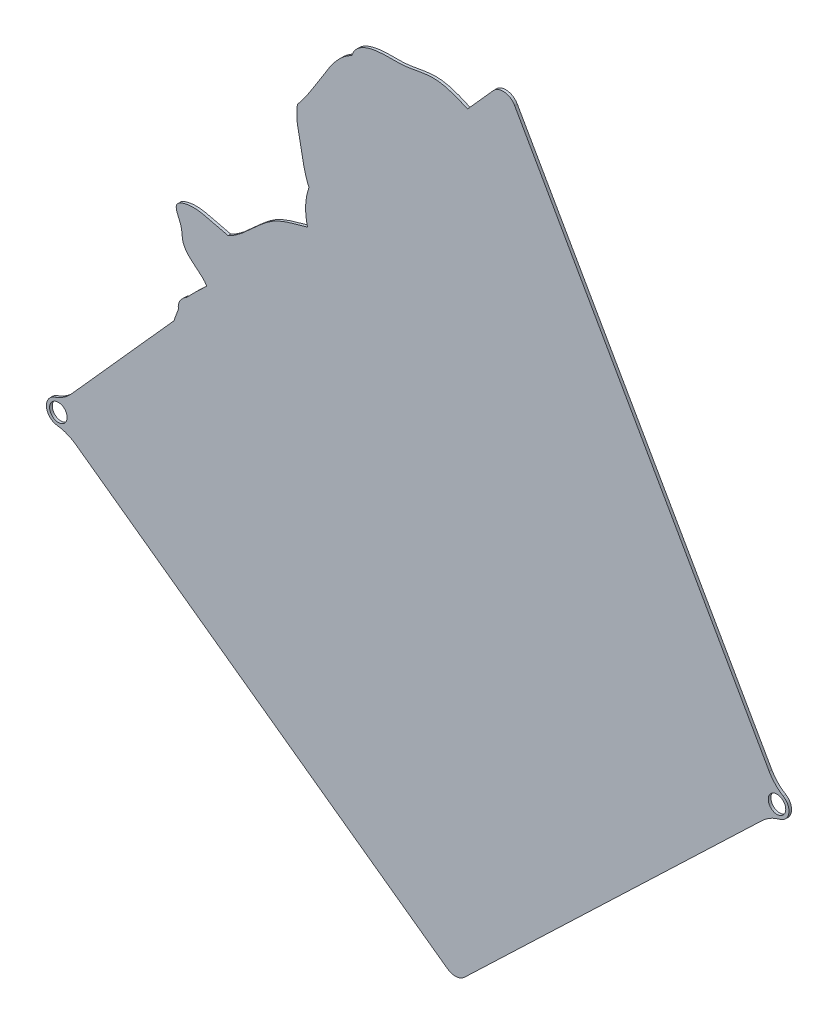
SolidWorks part; units mm, degrees
ref_plane "Front Plane" through (0, 0, 0) normal (0, 0, 1) x (1, 0, 0)
ref_plane "Top Plane" through (0, 0, 0) normal (0, 1, 0) x (1, 0, 0)
ref_plane "Right Plane" through (0, 0, 0) normal (1, 0, 0) x (0, 0, -1)
sketch "Sketch1" plane through (0, 0, 0) normal (0, 0, 1) x (1, 0, 0)
  line L0 (175.5305, 297.0782) -> (165.8477, 286.2471) construction
  line L1 (279.5133, 126.8993) -> (183.6087, 296.2101) construction
  line L2 (164.6882, 2.2459) -> (276.9577, 109.5557) construction
  line L3 (18.1895, 102.8728) -> (158.3084, 1.8052) construction
  line L4 (55.1562, 161.7513) -> (16.491, 118.5356) construction
  line L5 (175.5305, 297.0782) -> (165.8477, 286.2471)
  line L6 (279.5133, 126.8993) -> (183.6087, 296.2101)
  line L7 (164.6882, 2.2459) -> (276.9577, 109.5557)
  line L8 (18.1895, 102.8728) -> (158.3084, 1.8052)
  line L9 (55.1562, 161.7513) -> (16.491, 118.5356)
  arc A0 (56.8873, 166.4203) -> (55.1562, 161.7513) centre (192.7693, 113.3846) ccw construction
  arc A1 (183.6087, 296.2101) -> (175.5305, 297.0782) centre (179.2581, 293.7458) ccw construction
  circle A2 centre (11.6121, 110.083) radius 3.3
  arc A3 (158.3084, 1.8052) -> (164.6882, 2.2459) centre (161.2334, 5.8603) ccw construction
  circle A4 centre (282.4812, 117.6019) radius 3.3
  arc A5 (56.8873, 166.4203) -> (55.1562, 161.7513) centre (192.7693, 113.3846) ccw
  arc A6 (183.6087, 296.2101) -> (175.5305, 297.0782) centre (179.2581, 293.7458) ccw
  arc A8 (158.3084, 1.8052) -> (164.6882, 2.2459) centre (161.2334, 5.8603) ccw
  arc A10 (279.5133, 126.8993) -> (284.8082, 121.4535) centre (292.5649, 134.2923) ccw construction
  arc A11 (283.5983, 113.2428) -> (284.8082, 121.4535) centre (282.4812, 117.6019) ccw construction
  arc A12 (283.5983, 113.2428) -> (276.9577, 109.5557) centre (287.3221, 98.7123) ccw construction
  arc A13 (18.1895, 102.8728) -> (11.1049, 105.6117) centre (9.4145, 90.7073) ccw construction
  arc A14 (10.1582, 114.3417) -> (11.1049, 105.6117) centre (11.6121, 110.083) ccw construction
  arc A15 (10.1582, 114.3417) -> (16.491, 118.5356) centre (5.3122, 128.5373) ccw construction
  arc A16 (279.5133, 126.8993) -> (284.8082, 121.4535) centre (292.5649, 134.2923) ccw
  arc A17 (283.5983, 113.2428) -> (284.8082, 121.4535) centre (282.4812, 117.6019) ccw
  arc A18 (283.5983, 113.2428) -> (276.9577, 109.5557) centre (287.3221, 98.7123) ccw
  arc A19 (18.1895, 102.8728) -> (11.1049, 105.6117) centre (9.4145, 90.7073) ccw
  arc A20 (10.1582, 114.3417) -> (11.1049, 105.6117) centre (11.6121, 110.083) ccw
  arc A21 (10.1582, 114.3417) -> (16.491, 118.5356) centre (5.3122, 128.5373) ccw
  parabola Q0 (67.5512, 179.2621) -> (59.9806, 171.8401) focus (123.8149, 114.9886) apex (64.398, 176.2823) construction
  parabola Q1 (106.0756, 230.7794) -> (105.5434, 217.5484) focus (115.6832, 223.7852) apex (104.8052, 224.2398) construction
  parabola Q2 (67.5512, 179.2621) -> (59.9806, 171.8401) focus (123.8149, 114.9886) apex (64.398, 176.2823)
  parabola Q3 (106.0756, 230.7794) -> (105.5434, 217.5484) focus (115.6832, 223.7852) apex (104.8052, 224.2398)
  spline S0 degree 3 poles (-2645.6101, -1120.095) (2918.5612, 1295.9072) (-2873.9229, -730.4511) (2987.3572, 795.7907) knots -10.941247 -10.941247 -10.941247 -10.941247 11.131801 11.131801 11.131801 11.131801 only from (59.9806, 171.8401) to (56.8873, 166.4203) construction
  spline S1 degree 3 poles (-2656.9377, 1437.6987) (257.9264, 129.8839) (118.5279, 190.9741) (62.0198, 202.9668) (54.835, 201.0499) (56.9213, 196.4315) (58.3216, 193.1787) (58.0823, 189.1615) (80.0257, 158.7947) (179.564, 233.8845) (-1759.5569, -2199.2203) knots -3.74546 -3.74546 -3.74546 -3.74546 0.185123 0.320265 0.454108 0.537289 0.599178 0.70007 0.790197 2.992434 2.992434 2.992434 2.992434 only from (75.6084, 199.7873) to (67.5512, 179.2621) construction
  spline S2 degree 3 poles (-1350.5355, 2838.3581) (288.0292, 83.3372) (-17.7935, 402.6464) (109.909, -41.6201) (-1560.5, 2711.925) knots -4.166304 -4.166304 -4.166304 -4.166304 0.364395 5.175978 5.175978 5.175978 5.175978 only from (105.5434, 217.5484) to (75.6084, 199.7873) construction
  spline S3 degree 3 poles (3085.1277, 554.5988) (46.6808, 336.8237) (143.0301, 242.0054) (81.6341, 136.2882) (3065.0897, 714.166) knots -5.278013 -5.278013 -5.278013 -5.278013 0.517214 6.712304 6.712304 6.712304 6.712304 only from (101.7038, 255.6366) to (106.0756, 230.7794) construction
  spline S4 degree 3 poles (2166.8114, -1910.4258) (206.4667, 341.7319) (45.8762, 278.6153) (107.8222, 104.7999) (-2596.4092, 1558.7712) knots -4.24314 -4.24314 -4.24314 -4.24314 0.398896 7.217676 7.217676 7.217676 7.217676 only from (122.2298, 281.8784) to (101.7038, 255.6366) construction
  spline S5 degree 3 poles (-664.3616, 3168.8682) (264.6377, -4.7161) (207.2514, 308.5337) (142.9497, 287.9223) (98.2384, 291.1108) (12.8692, 211.827) (2552.1274, -1473.3212) knots -3.454803 -3.454803 -3.454803 -3.454803 0.28257 0.534959 0.697744 3.235991 3.235991 3.235991 3.235991 only from (165.8477, 286.2471) to (122.2298, 281.8784) construction
  spline S6 degree 3 poles (59.9806, 171.8401) (58.1352, 170.7697) (56.3909, 168.7153) (56.8873, 166.4203) knots 0 0 0 0 1 1 1 1
  spline S7 degree 3 poles (75.6084, 199.7873) (72.965, 200.4484) (68.1301, 201.67) (62.0198, 202.9668) (54.835, 201.0499) (56.9213, 196.4315) (58.3216, 193.1787) (58.0823, 189.1615) (61.7574, 184.0757) (65.8516, 182.0534) (67.5512, 179.2621) knots 0 0 0 0 0.185123 0.320265 0.454108 0.537289 0.599178 0.70007 0.790197 1 1 1 1
  spline S8 degree 3 poles (105.5434, 217.5484) (101.4789, 216.2752) (89.4383, 214.0041) (82.3649, 202.9844) (75.6084, 199.7873) knots 0 0 0 0 0.364395 1 1 1 1
  spline S9 degree 3 poles (101.7038, 255.6366) (100.9389, 251.2358) (103.1834, 242.9278) (104.3306, 234.5439) (106.0756, 230.7794) knots 0 0 0 0 0.517214 1 1 1 1
  spline S10 degree 3 poles (122.2298, 281.8784) (118.059, 279.823) (111.2357, 270.7398) (106.1066, 260.8139) (101.7038, 255.6366) knots 0 0 0 0 0.398896 1 1 1 1
  spline S11 degree 3 poles (165.8477, 286.2471) (161.959, 288.0532) (153.7542, 291.3856) (142.9497, 287.9223) (132.0887, 288.6969) (123.73, 286.7623) (122.2298, 281.8784) knots 0 0 0 0 0.28257 0.534959 0.697744 1 1 1 1
  dimension "D1" = 6.6
extrude "Boss-Extrude1" add sketch "Sketch1" against normal blind 1 from offset 3 offset against normal yes
